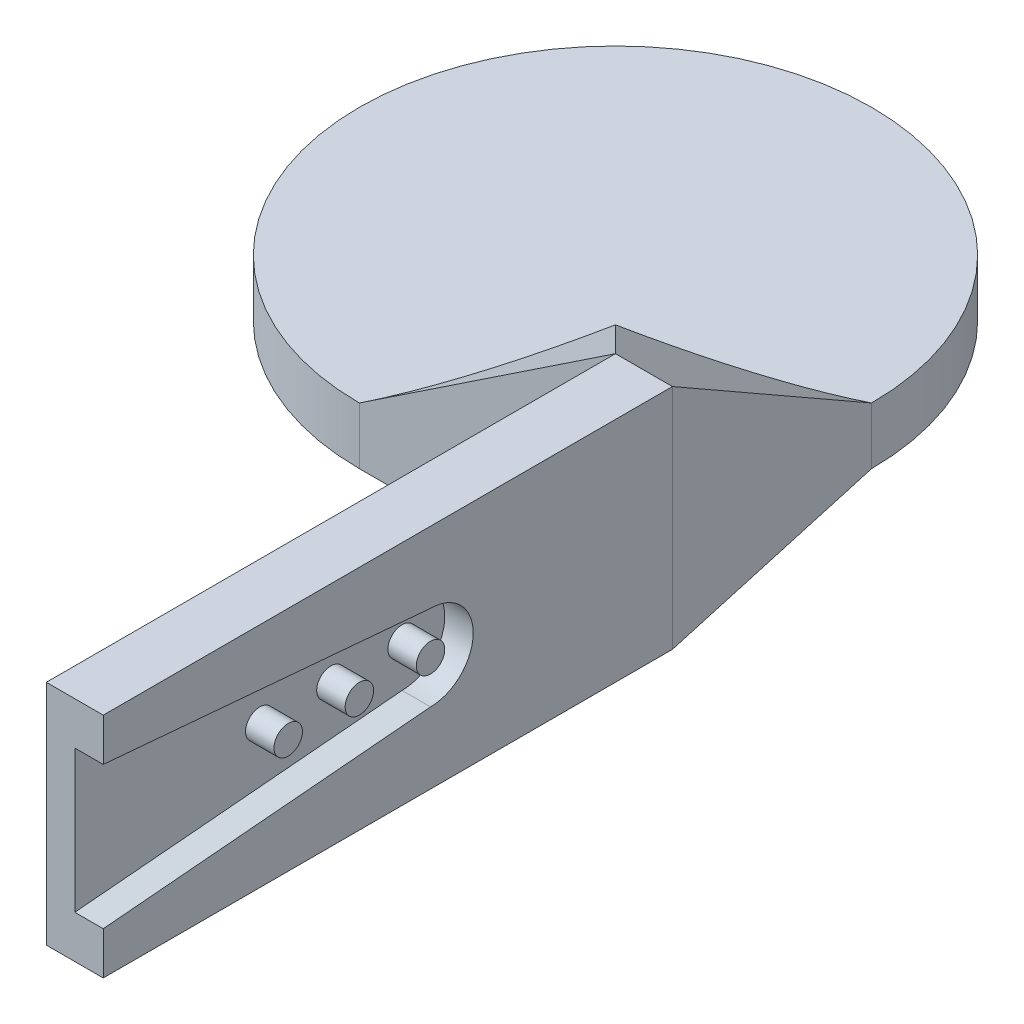
SolidWorks part; units mm, degrees
ref_plane "Front Plane" through (0, 0, 0) normal (0, 0, 1) x (1, 0, 0)
ref_plane "Top Plane" through (0, 0, 0) normal (0, 1, 0) x (1, 0, 0)
ref_plane "Right Plane" through (0, 0, 0) normal (1, 0, 0) x (0, 0, -1)
sketch "Sketch1" plane through (0, 0, 0) normal (0, 1, 0) x (1, 0, 0)
  line L0 (0, 0) -> (6.5, 0) construction
  line L1 (6.5, 1.5) -> (2, 1.5)
  line L2 (6.5, -1.5) -> (2, -1.5)
  line L3 (1.5, -6.5) -> (1.5, -2)
  line L4 (-1.5, -6.5) -> (-1.5, -2)
  line L5 (-6.5, -1.5) -> (-2, -1.5)
  line L6 (-6.5, 1.5) -> (-2, 1.5)
  line L7 (-1.5, 6.5) -> (-1.5, 2)
  line L8 (1.5, 6.5) -> (1.5, 2)
  line L9 (0, -9) -> (9, -9)
  line L10 (9, -9) -> (9, 0)
  line L11 (9, -9) -> (11, -9)
  line L12 (9, 0) -> (11, -9)
  line L13 (9, -9) -> (9, -29)
  line L14 (9, -29) -> (11, -29)
  line L15 (11, -29) -> (11, -9)
  circle A0 centre (0, 0) radius 1
  circle A1 centre (6.5, 0) radius 0.5
  circle A2 centre (0, 0) radius 2.5
  circle A4 centre (6.5, 0) radius 1.5
  circle A5 centre (0, -6.5) radius 1.5
  circle A6 centre (0, -6.5) radius 0.5
  circle A7 centre (-6.5, 0) radius 1.5
  circle A8 centre (-6.5, 0) radius 0.5
  circle A9 centre (0, 6.5) radius 1.5
  circle A10 centre (0, 6.5) radius 0.5
  circle A11 centre (0, 0) radius 9
  point P35 (0, 0)
  dimension "D1" = 4
extrude "Boss-Extrude1" add sketch "Sketch1" along normal blind 2 contours A10 | A8 | A6 | A1 | A0 | A0 A2 | A7 L5 A2 L6 | A7 A8 | A9 A10 | A9 L7 A2 L8 | A5 L3 A2 L4 | A2 L0 A4 L1 | L0 A2 L2 A4 | A4 A1 | A5 A6 | A11 A9 L8 A2 L1 A4 L2 L3 A5 L4 L5 A7 L6 L7 region at (2.3046, 0, 0.7682) region at (3.8465, 0, -0.8153) region at (3.8465, 0, 0.8153) region at (-0.9717, 0, 0) region at (6.5, 0, -0.4859) region at (5.4693, 0, -1.0307) region at (0, 0, -3.8465) region at (0, 0, 3.8465) region at (0, 0, -5.0424) region at (0, 0, 7.9576) region at (-3.8465, 0, 0) region at (-5.4693, 0, -1.0307) region at (-6.184, 0, -6.184) region at (0, 0, 6.5) region at (-6.5, 0, 0) region at (0, 0, -6.5)
extrude "Boss-Extrude2" add sketch "Sketch1<4>" along normal blind 8 contours A11 L9 L10 | L12 L10 L11 | L14 L15 L11 L13 region at (6.9897, 0, 6.9897) region at (9.6667, 0, 6) region at (10, 0, 19)
sketch "Sketch1<4>" plane through (0, 0, 0) normal (0, 1, 0) x (1, 0, 0) same geometry as "Sketch1"
extrude "Cut-Extrude1" cut sketch "Sketch1<5>" along normal blind 1 contours A5 A6 | A5 L3 A2 L4 | A7 L5 A2 L6 | A7 A8 | A0 A2 | A9 L7 A2 L8 | A9 A10 | A4 A1 | A2 L0 A4 L1 | L0 A2 L2 A4 | A0 region at (2.3046, 0, 0.7682) region at (3.8465, 0, -0.8153) region at (3.8465, 0, 0.8153) region at (-0.9717, 0, 0) region at (5.4693, 0, -1.0307) region at (0, 0, -3.8465) region at (0, 0, 3.8465) region at (0, 0, -5.0424) region at (0, 0, 7.9576) region at (-3.8465, 0, 0) region at (-5.4693, 0, -1.0307)
sketch "Sketch1<5>" plane through (0, 0, 0) normal (0, 1, 0) x (1, 0, 0) same geometry as "Sketch1"
sketch "Sketch2" plane through (0, 0, 9) normal (0, 0, 1) x (1, 0, 0)
  line L0 (0, 2) -> (9, 8)
  line L1 (9, 8) -> (0, 8)
  line L2 (0, 8) -> (0, 2)
extrude "Cut-Extrude2" cut sketch "Sketch2" against normal blind 9 contours L2 L0 L1
sketch "Sketch3" plane through (11, 0, 0) normal (1, 0, 0) x (0, 0, -1)
  line L0 (-9, 8) -> (0, 2)
  line L1 (0, 2) -> (0, 8)
  line L2 (0, 8) -> (-9, 8) construction
  line L3 (0, 8) -> (0, 2) construction
  line L4 (0, 8) -> (-9, 8)
extrude "Cut-Extrude3" cut sketch "Sketch3" against normal blind 9.986
sketch "Sketch4" plane through (11, 0, 0) normal (1, 0, 0) x (0, 0, -1)
  line L0 (-29, 8) -> (-29, 0) construction
  line L1 (-29, 4) -> (-17.5, 4) construction
  line L2 (-29, 6.5) -> (-17.5, 5.5)
  line L3 (-17.5, 2.5) -> (-29, 1.5)
  line L4 (-17.5, 4) -> (-20.448, 4) construction
  line L5 (-29, 4) -> (-22.5, 4) construction
  line L6 (-17.5, 4) -> (-20, 4) construction
  circle A0 centre (-29, 4) radius 2.5
  circle A1 centre (-17.5, 4) radius 0.5
  circle A2 centre (-17.5, 4) radius 1.5
  circle A4 centre (-22.5, 4) radius 0.5
  circle A5 centre (-20, 4) radius 0.5
  line M7 (-29, 8) -> (-29, 0)
extrude "Cut-Extrude5" cut sketch "Sketch4" against normal blind 1 contours L3 A0 L2 M7 | A2 L2 A0 L3 A5 A4 | A2 A1 region at (11, 4, 27.9385) region at (11, 4, 23.1616) region at (11, 5.0307, 16.4693)
